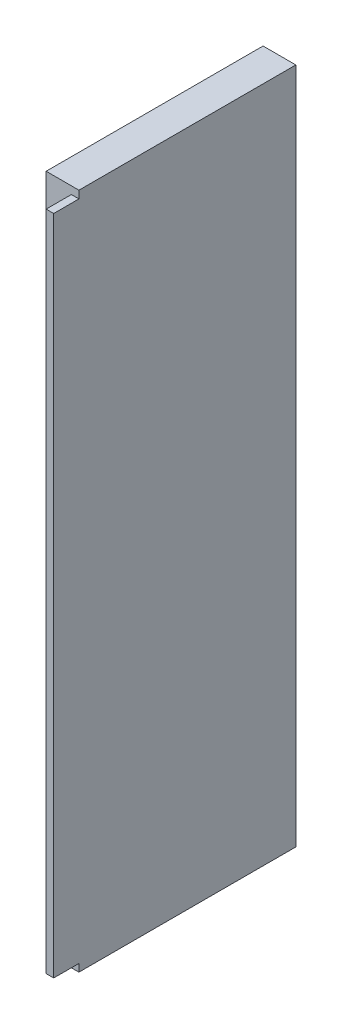
SolidWorks part; units mm, degrees
ref_plane "Front Plane" through (0, 0, 0) normal (0, 0, 1) x (1, 0, 0)
ref_plane "Top Plane" through (0, 0, 0) normal (0, 1, 0) x (1, 0, 0)
ref_plane "Right Plane" through (0, 0, 0) normal (1, 0, 0) x (0, 0, -1)
sketch "Sketch1" plane through (0, 0, 0) normal (0, 1, 0) x (1, 0, 0)
  line L0 (0, -16) -> (0, 16)
  line L1 (0, 16) -> (-4, 16)
  line L2 (-4, 16) -> (-4, 17.2)
  line L3 (-4, 17.2) -> (1.2, 17.2)
  line L4 (1.2, 17.2) -> (1.2, -17.2)
  line L5 (0, -17.2) -> (-4, -17.2)
  line L6 (-4, -17.2) -> (-4, -16)
  line L7 (-4, -16) -> (0, -16)
  line L8 (1.2, -17.2) -> (1.2, -21.2)
  line L9 (1.2, -21.2) -> (0, -21.2)
  line L10 (0, -21.2) -> (0, -17.2)
  point P4 (0, 0)
  dimension "D1" = 32
  dimension "D2" = 1.2
  dimension "D3" = 4
  dimension "D4" = 1.2
  dimension "D5" = 4
extrude "Boss-Extrude1" add sketch "Sketch1" along normal blind 105
sketch "Sketch2" plane through (0, 105, 0) normal (0, 1, 0) x (1, 0, 0)
  line L1 (1.2, 17.2) -> (-4, 17.2)
  line L2 (1.2, 17.2) -> (1.2, -17.2)
  line L3 (1.2, -17.2) -> (-4, -17.2)
  line L4 (-4, 17.2) -> (-4, -17.2)
extrude "Boss-Extrude2" add sketch "Sketch2" along normal blind 1.2
sketch "Sketch3" plane through (0, 0, 0) normal (0, -1, 0) x (1, 0, 0)
  line L1 (1.2, -17.2) -> (-4, -17.2)
  line L2 (1.2, -17.2) -> (1.2, 17.2)
  line L3 (1.2, 17.2) -> (-4, 17.2)
  line L4 (-4, -17.2) -> (-4, 17.2)
extrude "Boss-Extrude3" add sketch "Sketch3" along normal blind 1.2
sketch "Sketch4" plane through (0, 0, 0) normal (0, 1, 0) x (1, 0, 0)
  line L0 (0, 16) -> (0, -16) construction
  line L1 (0, -12.5) -> (-3, -12.5)
  line L2 (0, -12.5) -> (0, -9.5)
  line L3 (0, -9.5) -> (-3, -9.5)
  line L4 (-3, -12.5) -> (-3, -9.5)
  line L5 (0, -9.5) -> (0, -5.1667) construction
  line L6 (0, -5.1667) -> (-3, -5.1667)
  line L7 (0, -5.1667) -> (0, -2.1667)
  line L8 (0, -2.1667) -> (-3, -2.1667)
  line L9 (-3, -5.1667) -> (-3, -2.1667)
  line L10 (0, 2.1667) -> (-3, 2.1667)
  line L11 (0, 2.1667) -> (0, 5.1667)
  line L12 (0, 5.1667) -> (-3, 5.1667)
  line L13 (-3, 2.1667) -> (-3, 5.1667)
  line L14 (0, 9.5) -> (-3, 9.5)
  line L15 (0, 9.5) -> (0, 12.5)
  line L16 (0, 12.5) -> (-3, 12.5)
  line L17 (-3, 9.5) -> (-3, 12.5)
  line L18 (0, -2.1667) -> (0, 2.1667) construction
  line L19 (0, 5.1667) -> (0, 9.5) construction
  line L20 (-4, -16) -> (-4, 16) construction
  point P18 (0, 0)
  dimension "D1" = 3
  dimension "D2" = 22
  dimension "D3" = 1
extrude "Cut-Extrude1" cut sketch "Sketch4" against normal up to next
